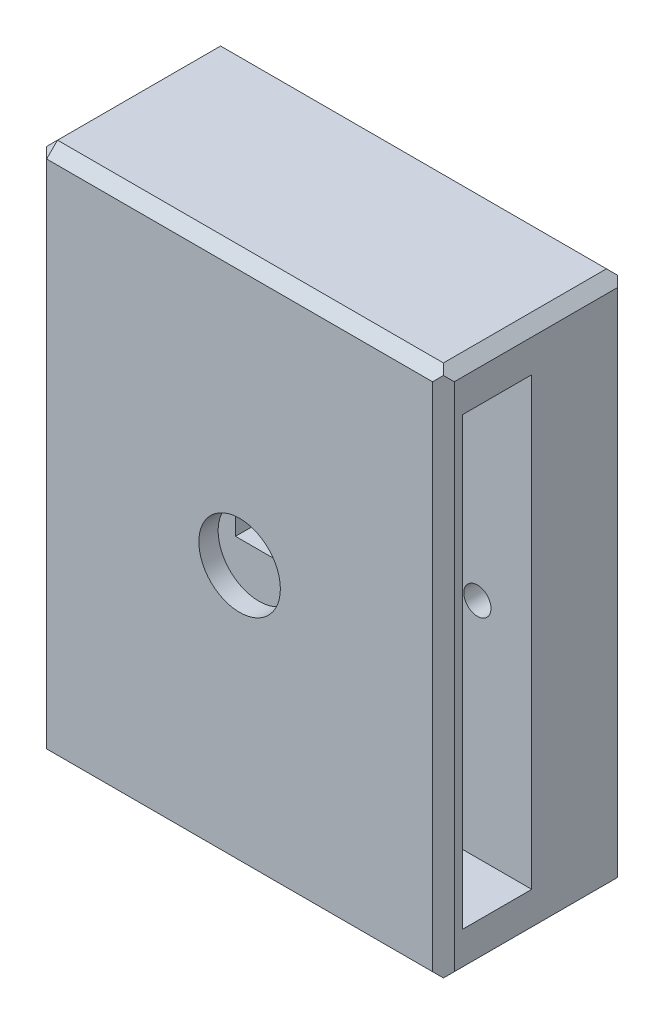
SolidWorks part; units mm, degrees
ref_plane "Front Plane" through (0, 0, 0) normal (0, 0, 1) x (1, 0, 0)
ref_plane "Top Plane" through (0, 0, 0) normal (0, 1, 0) x (1, 0, 0)
ref_plane "Right Plane" through (0, 0, 0) normal (1, 0, 0) x (0, 0, -1)
sketch "Sketch1" plane through (0, 0, 0) normal (0, 1, 0) x (1, 0, 0)
  line L1 (0, 0) -> (50, 0)
  line L2 (0, 0) -> (0, 25)
  line L3 (0, 25) -> (50, 25)
  line L4 (50, 0) -> (50, 25)
  dimension "D1" = 25
  dimension "D2" = 50
extrude "Boss-Extrude1" add sketch "Sketch1" along normal blind 49
sketch "Sketch4" plane through (50, 0, 0) normal (1, 0, 0) x (0, 0, -1)
  line L0 (25, 49) -> (25, 0) construction
  line L1 (9.775, 45) -> (16.125, 45)
  line L2 (9.775, 45) -> (9.775, 35.25)
  line L4 (16.125, 45) -> (16.125, 34.1275)
  line L9 (9.775, 13.75) -> (9.775, 35.25)
  line L10 (0, 49) -> (25, 49) construction
  line L11 (0, 0) -> (25, 0) construction
  line L13 (9.775, 13.75) -> (9.775, 4)
  line L14 (9.775, 4) -> (16.125, 4)
  line L15 (16.125, 12.6275) -> (16.125, 4)
  line L16 (16.125, 34.1275) -> (16.125, 12.6275)
  dimension "D1" = 6.35
  dimension "D2" = 8.875
  dimension "D3" = 4
  dimension "D4" = 9.75
  dimension "D5" = 6.4484
  dimension "D6" = 9.75
  dimension "D7" = 4
  dimension "D8" = 8.875
  dimension "D9" = 6.4484
sketch "Sketch5" plane through (0, 0, -25) normal (0, 0, -1) x (-1, 0, 0)
  line L0 (-50, 49) -> (0, 49) construction
  line L1 (0, 49) -> (0, 0) construction
  line L3 (-29.75, 30.5) -> (-10.25, 30.5)
  line L4 (-29.75, 30.5) -> (-29.75, 18.5)
  line L5 (-29.75, 18.5) -> (-10.25, 18.5)
  line L6 (-10.25, 30.5) -> (-10.25, 18.5)
  circle A0 centre (-25, 24.5) radius 2.5 construction
  circle A1 centre (-32.5, 24.5) radius 1.25
  circle A2 centre (-7.5, 24.5) radius 1.25
  dimension "D1" = 24.5
  dimension "D2" = 25
  dimension "D3" = 5
  dimension "D5" = 2.5
  dimension "D7" = 2.5
  dimension "D4" = 7.5
  dimension "D6" = 17.5
  dimension "D8" = 7.5
  dimension "D9" = 2.75
  dimension "D10" = 2.75
  dimension "D11" = 12
  dimension "D12" = 6
extrude "Cut-Extrude2" cut sketch "Sketch4" against normal blind 55
extrude "Cut-Extrude3" cut sketch "Sketch5" against normal blind 12.5
sketch "Sketch7" plane through (0, 0, 0) normal (0, 0, 1) x (1, 0, 0)
  line L1 (0, 49) -> (50, 49)
  line L2 (0, 49) -> (0, 0)
  line L3 (0, 0) -> (50, 0)
  line L4 (50, 49) -> (50, 0)
extrude "Cut-Extrude4" cut sketch "Sketch7" against normal blind 8
chamfer "Chamfer1" distance 1 angle 45 12 edges at (50, 49, -16.5) (50, 0, -16.5) (0, 0, -16.5) (0, 24.5, -8) (25, 0, -8) (50, 24.5, -8) (25, 49, -8) (0, 49, -16.5) (0, 24.5, -25) (25, 0, -25) (50, 24.5, -25) (25, 49, -25)
sketch "Sketch8" plane through (50, 0, 0) normal (1, 0, 0) x (0, 0, -1)
  line L0 (9, 48) -> (9, 1) construction
  line L1 (25.1746, 49.1529) -> (7.6347, 49.1529)
  line L2 (25.1746, 49.1529) -> (25.1746, -0.4165)
  line L3 (25.1746, -0.4165) -> (7.6347, -0.4165)
  line L4 (7.6347, 49.1529) -> (7.6347, -0.4165)
  line L5 (24, 48) -> (9, 48) construction
  dimension "D1" = 49.5694
  dimension "D2" = 17.54
  dimension "D3" = 1.3653
  dimension "D4" = 1.1529
extrude "Cut-Extrude5" cut sketch "Sketch8" against normal blind 12.5
chamfer "Chamfer2" distance 1 angle 45 4 edges at (37.5, 0, -16.5) (37.5, 49, -16.5) (37.5, 24.5, -8) (37.5, 24.5, -25)
sketch "Sketch9" plane through (0, 0, -8) normal (0, 0, 1) x (1, 0, 0)
  line L0 (36.5, 1) -> (36.5, 48) construction
  line L2 (36.5, 48) -> (1, 48) construction
  circle A0 centre (18.75, 24.5) radius 3.75
  dimension "D3" = 7.5
  dimension "D1" = 17.75
  dimension "D2" = 23.5
extrude "Cut-Extrude6" cut sketch "Sketch9" against normal blind 4
